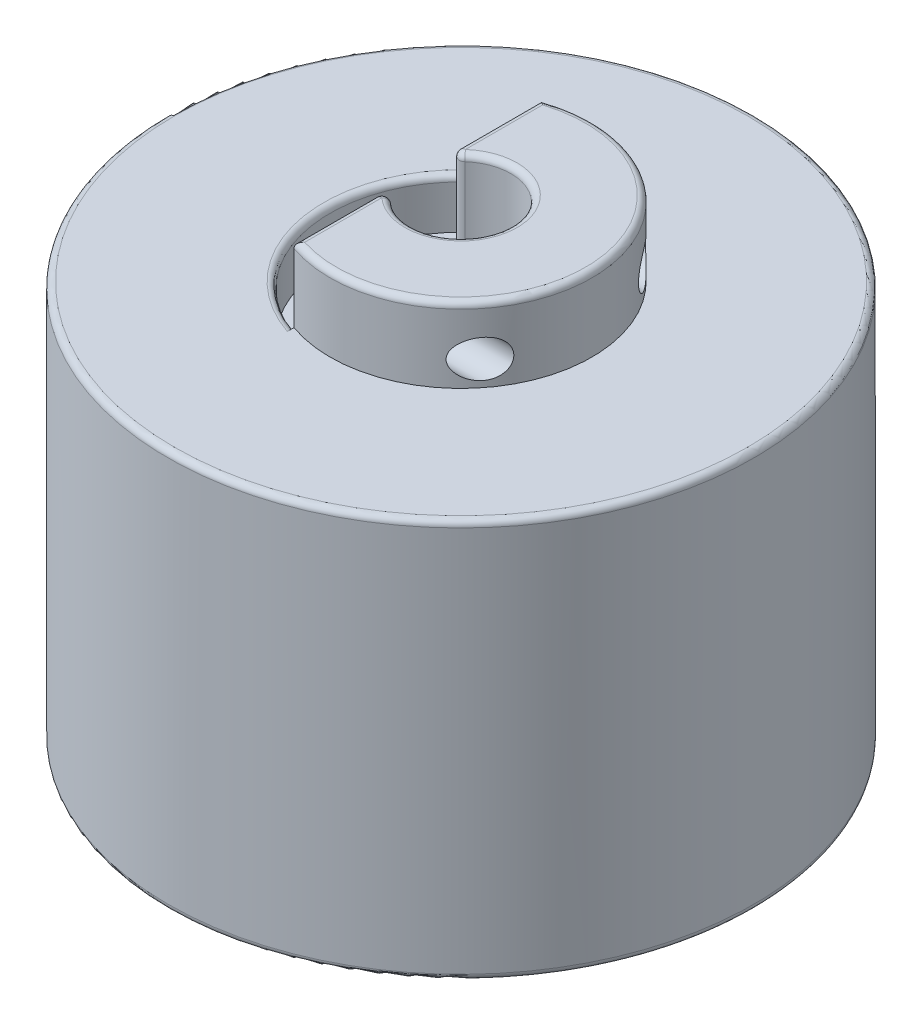
SolidWorks part; units mm, degrees
ref_plane "Front" through (0, 0, 0) normal (0, 0, 1) x (1, 0, 0)
ref_plane "Top" through (0, 0, 0) normal (0, 1, 0) x (1, 0, 0)
ref_plane "Right" through (0, 0, 0) normal (1, 0, 0) x (0, 0, -1)
sketch "Esquisse1" plane through (0, 0, 0) normal (0, 0, 1) x (1, 0, 0)
  line L0 (0, 0) -> (0, 59.5454) construction
  line L1 (-19.5, 0) -> (-23.5, 0)
  line L2 (-23.5, 0) -> (-23.5, 32)
  line L3 (-23.5, 32) -> (-10.5, 32)
  line L4 (-10.5, 32) -> (-10.5, 38)
  line L5 (-10.5, 38) -> (0, 38)
  line L6 (0, 38) -> (0, 23)
  line L7 (0, 23) -> (-19.5, 23)
  line L8 (-19.5, 23) -> (-19.5, 0)
  dimension "D1" = 4
  dimension "D2" = 23
  dimension "D3" = 39
  dimension "D4" = 32
  dimension "D5" = 21
  dimension "D6" = 38
revolve "Révolution1" add sketch "Esquisse1" angle 360 about L0
sketch "Esquisse2" plane through (0, 38, 0) normal (0, 1, 0) x (1, 0, 0)
  circle A0 centre (0, 0) radius 4
  dimension "D1" = 8
extrude "Enlèv. mat.-Extru.1" cut sketch "Esquisse2" against normal blind 20
sketch "Esquisse3" plane through (0, 38, 0) normal (0, 1, 0) x (1, 0, 0)
  line L0 (-3.5, 9.8995) -> (-3.5, -9.8995)
  line L1 (10.5, 6.7809) -> (10.5, -6.8809) construction
  circle A0 centre (0, 0) radius 10.5 construction
  circle A1 centre (0, 0) radius 10.5 construction
  circle A2 centre (0, 0) radius 10.5
  circle M3 centre (0, 0) radius 4
  circle M4 centre (0, 0) radius 10.5
  dimension "D1" = 14
extrude "Enlèv. mat.-Extru.2" cut sketch "Esquisse3" against normal blind 10 contours L0 M4 M3 region at (-6.4349, 38, 0)
sketch "Esquisse5" plane through (-3.5, 0, 0) normal (-1, 0, 0) x (0, 0, 1)
  line L0 (-6.5, 34) -> (6.5, 34) construction
  line L1 (0, 34) -> (0, 38) construction
  line L2 (4, 38) -> (-4, 38) construction
  line L3 (-9.8995, 38) -> (-1.9365, 38) construction
  circle A0 centre (-6.5, 34) radius 1.5
  circle A1 centre (6.5, 34) radius 1.5
  dimension "D3" = 3
  dimension "D1" = 13
  dimension "D2" = 4
extrude "Enlèv. mat.-Extru.3" cut sketch "Esquisse5" against normal blind 15
fillet "Congé1" radius 0.5 2 edges at (-3.5, 33, 1.9365) (-3.5, 33, -1.9365)
fillet "Congé2" radius 0.5 12 edges at (0, 0, -19.5) (0, 23, -19.5) (-3.2041, 38, -2.8977) (-3.5, 38, -6.6268) (10.5, 38, 0) (-3.5, 38, 6.6268) (-3.2041, 38, 2.8977) (4, 38, 0) (0, 32, -23.5) (0, 0, -23.5) (0, 23, 4) (-10.5, 32, 0)
